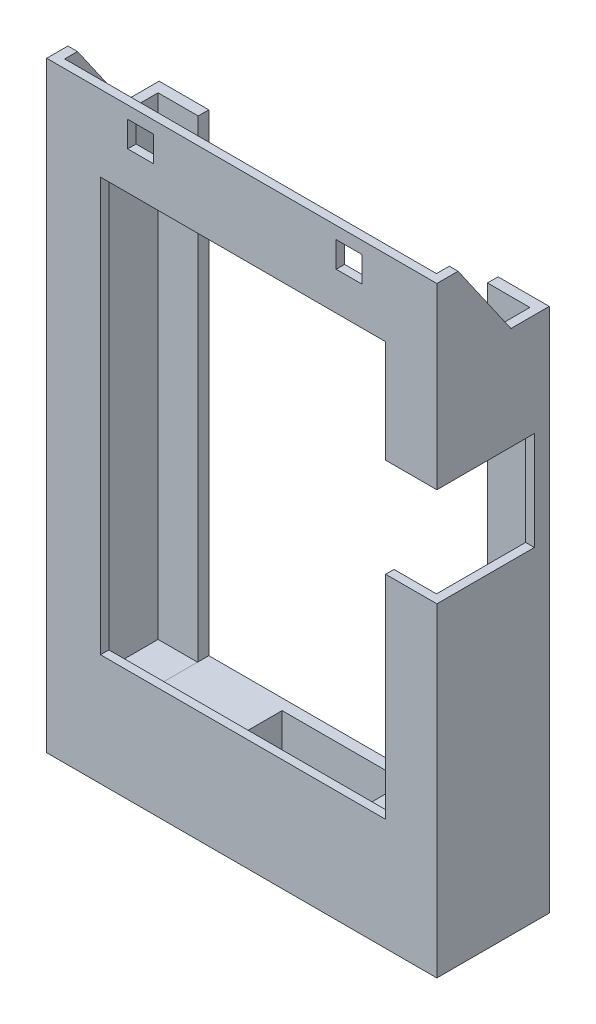
SolidWorks part; units mm, degrees
ref_plane "Front Plane" through (0, 0, 0) normal (0, 0, 1) x (1, 0, 0)
ref_plane "Top Plane" through (0, 0, 0) normal (0, 1, 0) x (1, 0, 0)
ref_plane "Right Plane" through (0, 0, 0) normal (1, 0, 0) x (0, 0, -1)
sketch "Sketch4" plane through (0, 0, 0) normal (0, 0, 1) x (1, 0, 0)
  line L1 (60, 92.5) -> (-60, 92.5)
  line L2 (60, 92.5) -> (60, -92.5)
  line L3 (60, -92.5) -> (-60, -92.5)
  line L4 (-60, 92.5) -> (-60, -92.5)
  line L5 (60, 92.5) -> (-60, -92.5) construction
  line L6 (60, -92.5) -> (-60, 92.5) construction
  point P0 (0, 0)
  dimension "D1" = 120
  dimension "D2" = 185
extrude "Boss-Extrude2" add sketch "Sketch4" along normal blind 34.4794 and the other way blind 0.1
sketch "Sketch7" plane through (0, 0, -0.1) normal (0, 0, -1) x (-1, 0, 0)
  line L0 (-60, 92.5) -> (60, 92.5) construction
  line L1 (-44.2434, 92.5) -> (44.7217, 92.5)
  line L2 (-44.2434, 92.5) -> (-44.2434, -76.29)
  line L3 (-44.2434, -76.29) -> (44.7217, -76.29)
  line L4 (44.7217, 92.5) -> (44.7217, -76.29)
extrude "Cut-Extrude1" cut sketch "Sketch7" against normal blind 32
sketch "Sketch8" plane through (0, -76.29, 0) normal (0, 1, 0) x (1, 0, 0)
  line L1 (-18.8197, -3.2559) -> (19.2992, -3.2559)
  line L2 (-18.8197, -3.2559) -> (-18.8197, -29.2679)
  line L3 (-18.8197, -29.2679) -> (19.2992, -29.2679)
  line L4 (19.2992, -3.2559) -> (19.2992, -29.2679)
extrude "Cut-Extrude2" cut sketch "Sketch8" against normal blind 32
sketch "Sketch12" plane through (0, 92.5, 0) normal (0, 1, 0) x (1, 0, 0)
  line L1 (-44.7217, -31.9) -> (-57.0584, -31.9)
  line L2 (-44.7217, -31.9) -> (-44.7217, -3.1648)
  line L3 (-44.7217, -3.1648) -> (-57.0584, -3.1648)
  line L4 (-57.0584, -31.9) -> (-57.0584, -3.1648)
  line L5 (44.2434, -31.9) -> (57.2982, -31.9)
  line L6 (44.2434, -31.9) -> (44.2434, -3.1648)
  line L7 (44.2434, -3.1648) -> (57.2982, -3.1648)
  line L8 (57.2982, -31.9) -> (57.2982, -3.1648)
extrude "Cut-Extrude10" cut sketch "Sketch12" against normal blind 169
sketch "Sketch13" plane through (60, 0, 0) normal (1, 0, 0) x (0, 0, -1)
  line L0 (-27.9521, 92.5) -> (-11.6897, 69.1154)
  line L1 (0.1, 92.5) -> (-34.4794, 92.5) construction
  line L2 (-11.6897, 69.1154) -> (0.1, 69.1154)
  line L3 (0.1, -92.5) -> (0.1, 92.5) construction
extrude "Cut-Extrude11" cut sketch "Sketch13" against normal blind 120 and the other way through all
sketch "Sketch14" plane through (0, 0, 31.9) normal (0, 0, -1) x (-1, 0, 0)
  line L1 (-36.93, 88.7053) -> (-29.0366, 88.7053)
  line L2 (-36.93, 88.7053) -> (-36.93, 80.8118)
  line L3 (-36.93, 80.8118) -> (-29.0366, 80.8118)
  line L4 (-29.0366, 88.7053) -> (-29.0366, 80.8118)
  line L5 (35.1022, 88.7053) -> (27.2088, 88.7053)
  line L6 (35.1022, 88.7053) -> (35.1022, 80.8118)
  line L7 (35.1022, 80.8118) -> (27.2088, 80.8118)
  line L8 (27.2088, 88.7053) -> (27.2088, 80.8118)
extrude "Cut-Extrude13" cut sketch "Sketch14" against normal blind 120
sketch "Sketch16" plane through (0, 0, 34.4794) normal (0, 0, 1) x (1, 0, 0)
  line L0 (60, -92.5) -> (60, 92.5) construction
  line L1 (60, 37.5471) -> (43.7651, 37.5471)
  line L2 (60, 37.5471) -> (60, 7.1746)
  line L3 (60, 7.1746) -> (43.7651, 7.1746)
  line L4 (43.7651, 37.5471) -> (43.7651, 7.1746)
extrude "Cut-Extrude15" cut sketch "Sketch16" against normal blind 30
sketch "Sketch18" plane through (0, 0, 34.4794) normal (0, 0, 1) x (1, 0, 0)
  line L0 (44.2434, -76.29) -> (44.2434, 69.1154) construction
  line L1 (44.2434, 69.1154) -> (-43.4529, 69.1154)
  line L2 (44.2434, 69.1154) -> (44.2434, -58.1193)
  line L3 (44.2434, -58.1193) -> (-43.4529, -58.1193)
  line L4 (-43.4529, 69.1154) -> (-43.4529, -58.1193)
extrude "Cut-Extrude20" cut sketch "Sketch18" against normal blind 10 contours L3 L4 L1 L2
